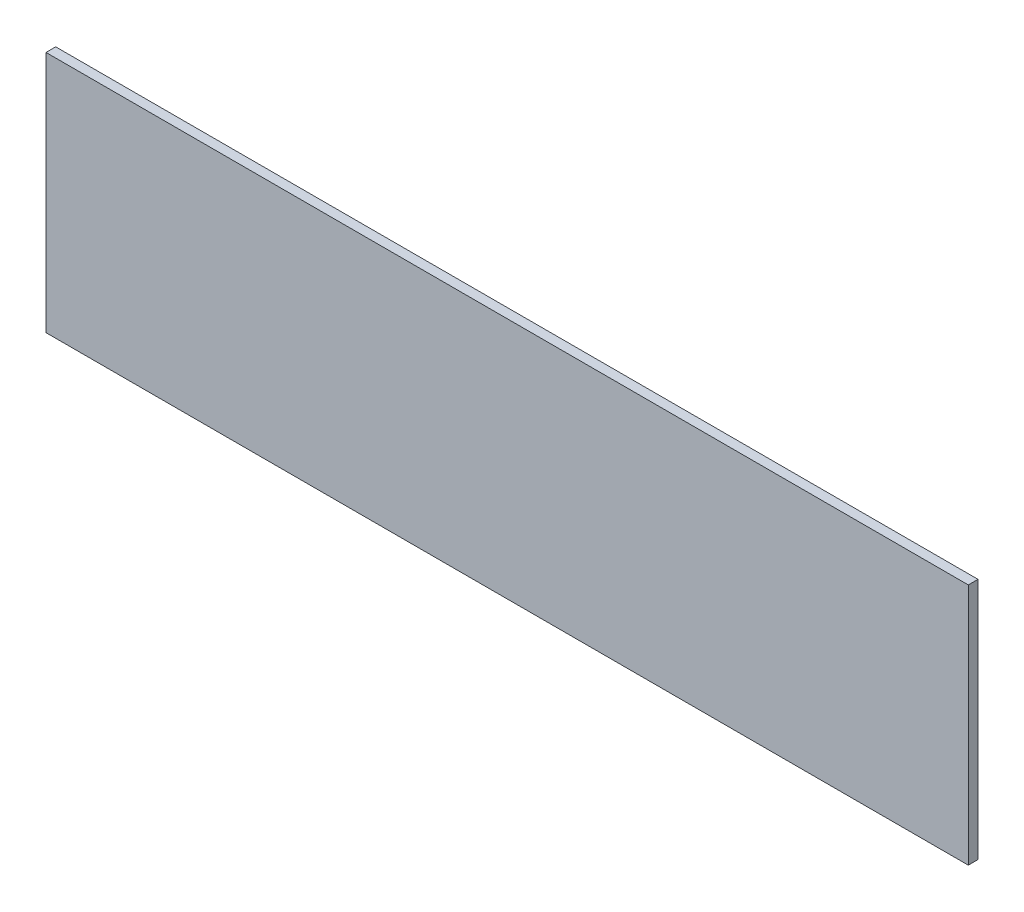
SolidWorks part; units mm, degrees
ref_plane "Plan de face" through (0, 0, 0) normal (0, 0, 1) x (1, 0, 0)
ref_plane "Plan de dessus" through (0, 0, 0) normal (0, 1, 0) x (1, 0, 0)
ref_plane "Plan de droite" through (0, 0, 0) normal (1, 0, 0) x (0, 0, -1)
sketch "Esquisse1" plane through (0, 0, 0) normal (0, 0, 1) x (1, 0, 0)
  line L1 (-139.4457, 100.7193) -> (240.5543, 100.7193)
  line L2 (-139.4457, 100.7193) -> (-139.4457, 0.7193)
  line L3 (-139.4457, 0.7193) -> (240.5543, 0.7193)
  line L4 (240.5543, 100.7193) -> (240.5543, 0.7193)
  dimension "D1" = 380
  dimension "D2" = 100
extrude "Boss.-Extru.1" add sketch "Esquisse1" along normal blind 4
